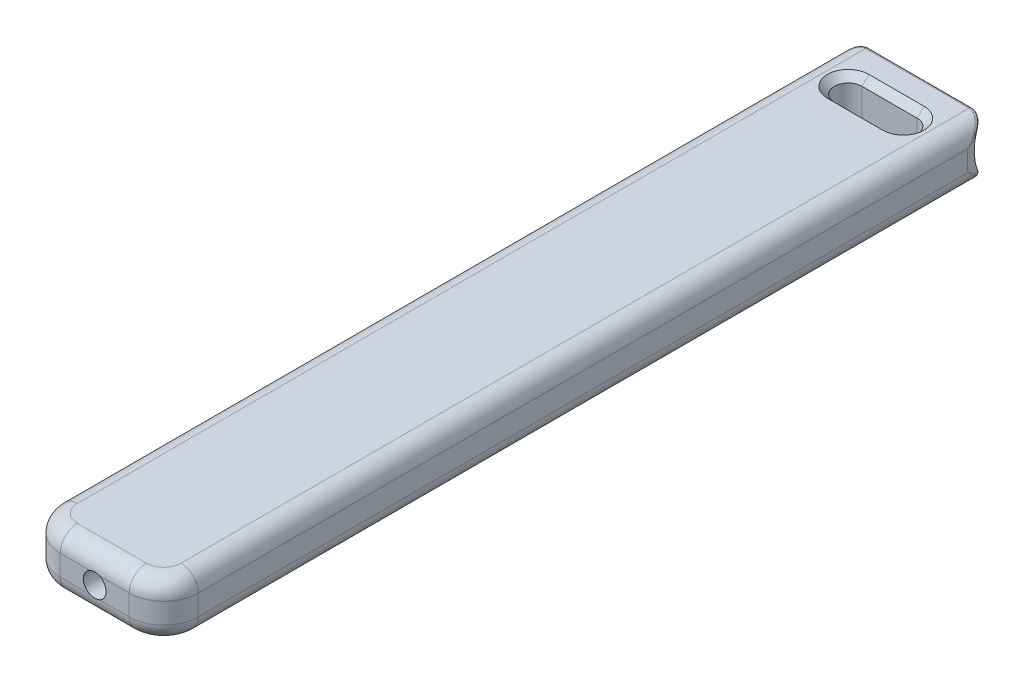
SolidWorks part; units mm, degrees
ref_plane "前基準面" through (0, 0, 0) normal (0, 0, 1) x (1, 0, 0)
ref_plane "上基準面" through (0, 0, 0) normal (0, 1, 0) x (1, 0, 0)
ref_plane "右基準面" through (0, 0, 0) normal (1, 0, 0) x (0, 0, -1)
sketch "草圖1" plane through (0, 0, 0) normal (0, 1, 0) x (1, 0, 0)
  line L1 (-10, 60) -> (10, 60)
  line L2 (-10, 60) -> (-10, -60)
  line L3 (-10, -60) -> (10, -60)
  line L4 (10, 60) -> (10, -60)
  line L5 (-10, 60) -> (10, -60) construction
  line L6 (-10, -60) -> (10, 60) construction
  point P0 (0, 0)
extrude "填料-伸長1" add sketch "草圖1" along normal blind 8
ref_plane "平面1" through (0, 0, 60) normal (0, 0, 1) x (1, 0, 0)
sketch "草圖2" plane through (0, 0, 60) normal (0, 0, 1) x (1, 0, 0)
  line L0 (-10, 4) -> (10, 4)
  line L1 (-10, 8) -> (-10, 0) construction
  line L2 (10, 8) -> (10, 0) construction
  circle A0 centre (0, 4) radius 1.5
  point P6 (0, 4)
extrude "除料-伸長1" cut sketch "草圖2" against normal blind 10 contours L0 A0 | L0 A0 region at (0, 4.6366, 60) region at (0, 3.3634, 60)
sketch "草圖3" plane through (0, 0, 60) normal (0, 0, 1) x (1, 0, 0)
  circle A0 centre (0, 4) radius 1.65
  dimension "D1" = 3.3
extrude "除料-伸長2_m4" cut sketch "草圖3" against normal blind 10
sketch "草圖4" plane through (10, 0, 0) normal (1, 0, 0) x (0, 0, -1)
  line L0 (60, 8) -> (60, 0)
  arc A0 (60, 8) -> (60, 0) centre (66.9282, 4) ccw
extrude "除料-伸長3" cut sketch "草圖4" against normal through all
fillet "圓角2" radius 5 2 edges at (-10, 4, 60) (10, 4, 60)
fillet "圓角3" radius 2.5 12 edges at (10, 8, -2.5) (8.5355, 8, 58.5355) (0, 8, 60) (-8.5355, 8, 58.5355) (10, 0, -2.5) (8.5355, 0, 58.5355) (0, 0, 60) (-8.5355, 0, 58.5355) (-10, 4, -58.9282) (-10, 8, -2.5) (-10, 0, -2.5) (10, 4, -58.9282)
fillet "圓角1" radius 0.5 6 edges at (0, 0, -60) (0, 8, -60) (8.4467, 0.1862, -59.6847) (-8.4467, 0.1862, -59.6847) (8.4467, 7.8138, -59.6847) (-8.4467, 7.8138, -59.6847)
sketch "草圖5" plane through (0, 8, 0) normal (0, 1, 0) x (1, 0, 0)
  line L0 (-7.5, 59.1822) -> (7.5, 59.1822)
  line L1 (0, 59.1822) -> (0, 53.1822)
  line L2 (-4, 53.1822) -> (4, 53.1822) construction
  line L3 (-4, 55.1822) -> (4, 55.1822)
  line L4 (-4, 51.1822) -> (4, 51.1822)
  arc A0 (-4, 55.1822) -> (-4, 51.1822) centre (-4, 53.1822) ccw
  arc A1 (4, 51.1822) -> (4, 55.1822) centre (4, 53.1822) ccw
  point P9 (0, 53.1822)
  dimension "D1" = 8
  dimension "D2" = 2
  dimension "D3" = 6
extrude "除料-伸長4" cut sketch "草圖5" against normal blind 10 contours L4 A1 L3 A0 region at (-2, 8, -55.0557)
chamfer "導角4" distance 1 angle 45 8 edges at (0, 0, -55.1822) (-6, 0, -53.1822) (6, 0, -53.1822) (0, 0, -51.1822) (0, 8, -51.1822) (-6, 8, -53.1822) (6, 8, -53.1822) (0, 8, -55.1822)
